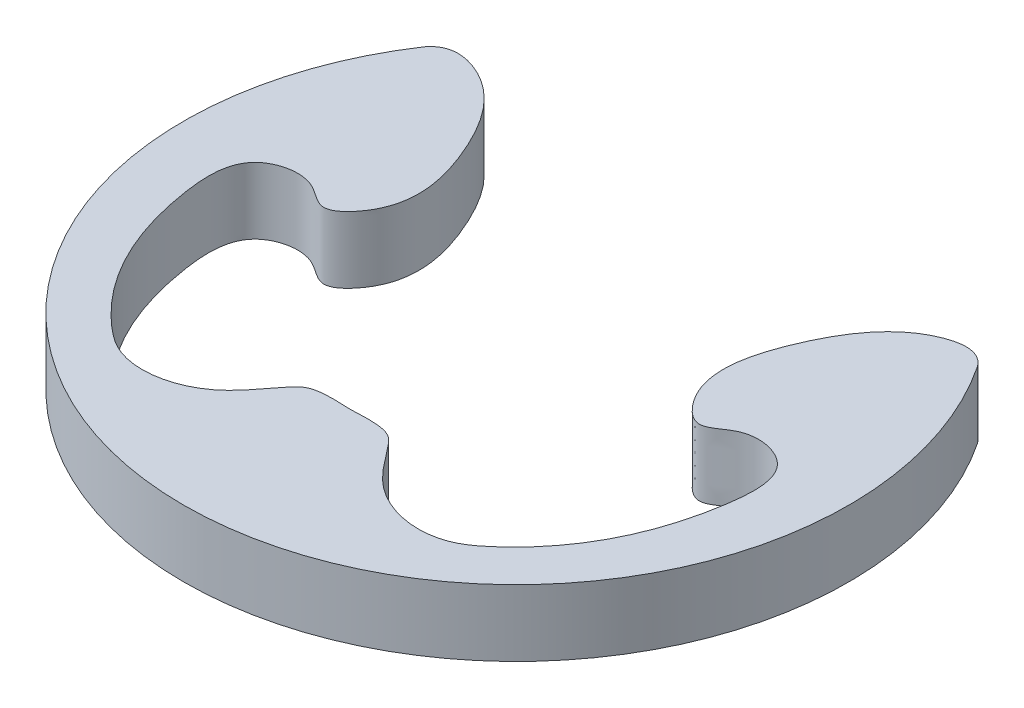
SolidWorks part; units mm, degrees
ref_plane "Front Plane" through (0, 0, 0) normal (0, 0, 1) x (1, 0, 0)
ref_plane "Top Plane" through (0, 0, 0) normal (0, 1, 0) x (1, 0, 0)
ref_plane "Right Plane" through (0, 0, 0) normal (1, 0, 0) x (0, 0, -1)
sketch "Sketch1" plane through (0, 0, 0) normal (0, 1, 0) x (1, 0, 0)
  circle A0 centre (0, 0) radius 2
  dimension "D1" = 4
extrude "Boss-Extrude1" add sketch "Sketch1" along normal blind 0.4
sketch "Sketch2" plane through (0, 0.4, 0) normal (0, 1, 0) x (1, 0, 0)
  line L0 (0, 2) -> (0, -2) construction
  circle A0 centre (0, 0) radius 2 construction
  circle A1 centre (0, 0) radius 1
  circle A2 centre (0, 0) radius 2
  spline S0 degree 3 poles (0, -1) (0.2083, -0.9882) (0.2857, -1.0252) (0.5161, -1.395) (0.9193, -1.4671) (1.3833, -1.1055) (1.6235, -0.6357) (1.6609, 0.031) (1.3057, 0.1106) (1.1336, -0.0762) (0.849, 0.1924) (0.9658, 0.7035) (1.2697, 1.1616) (1.6126, 1.2021) (1.6793, 1.0863) knots 0 0 0 0 0.062886 0.124136 0.231355 0.267285 0.479704 0.55555 0.615511 0.65108 0.684138 0.810147 0.937554 1 1 1 1
  spline S1 degree 3 poles (0, -1) (-0.2083, -0.9882) (-0.2857, -1.0252) (-0.5161, -1.395) (-0.9193, -1.4671) (-1.3833, -1.1055) (-1.6235, -0.6357) (-1.6609, 0.031) (-1.3057, 0.1106) (-1.1336, -0.0762) (-0.849, 0.1924) (-0.9658, 0.7035) (-1.2697, 1.1616) (-1.6126, 1.2021) (-1.6793, 1.0863) knots 0 0 0 0 0.062886 0.124136 0.231355 0.267285 0.479704 0.55555 0.615511 0.65108 0.684138 0.810147 0.937554 1 1 1 1
  circle M2 centre (0, 0) radius 2
  dimension "D1" = 2
extrude "Cut-Extrude1" cut sketch "Sketch2" against normal up to next contours L0 S1 A1 M2 | A2 L0 A1 S0 | A1 L0 S0 | A1 S0 | L0 A1 S1 | S1 A1 region at (-0.4208, 0.4, 0.0015) region at (0.4208, 0.4, 0.0015) region at (-0.6585, 0.4, -1.335) region at (0.6585, 0.4, -1.335) region at (-1.057, 0.4, 0.722) region at (1.057, 0.4, 0.722)
